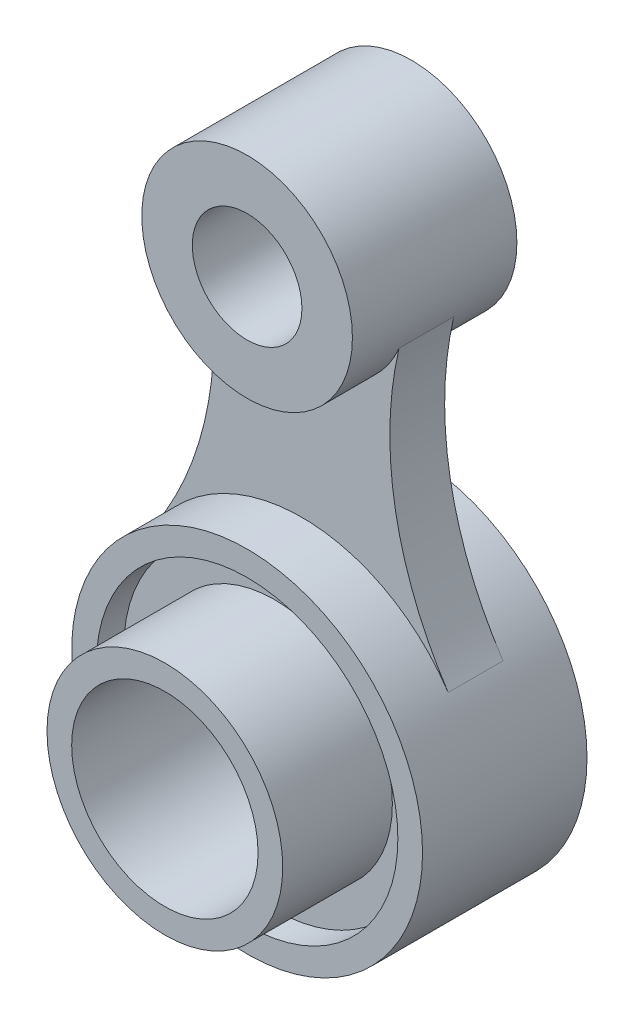
SolidWorks part; units mm, degrees
ref_plane "Front Plane" through (0, 0, 0) normal (0, 0, 1) x (1, 0, 0)
ref_plane "Top Plane" through (0, 0, 0) normal (0, 1, 0) x (1, 0, 0)
ref_plane "Right Plane" through (0, 0, 0) normal (1, 0, 0) x (0, 0, -1)
sketch "Sketch1" plane through (0, 0, 0) normal (0, 0, 1) x (1, 0, 0)
  line L0 (0, -38.5936) -> (0, 36.4064) construction
  circle A0 centre (0, -38.5936) radius 17
  circle A1 centre (0, -38.5936) radius 21.5
  circle A2 centre (0, -38.5936) radius 27.5
  arc A3 (-26.6783, -20.9225) -> (26.6783, -20.9225) centre (0, -38.5936) ccw
  arc A4 (18.3212, 31.3733) -> (-18.3212, 31.3733) centre (0, 36.4064) ccw
  circle A5 centre (0, 36.4064) radius 10
  arc A6 (26.6783, -20.9225) -> (18.3212, 31.3733) centre (80.0349, 14.4197) cw
  arc A7 (-26.6783, -20.9225) -> (-18.3212, 31.3733) centre (-80.0349, 14.4197) ccw
  circle A8 centre (0, 36.4064) radius 19.2117
  circle A9 centre (0, -38.5936) radius 32
  dimension "D1" = 34
  dimension "D2" = 43
  dimension "D3" = 55
  dimension "D4" = 64
  dimension "D5" = 38
  dimension "D6" = 20
  dimension "D8" = 64
  dimension "D7" = 75
extrude "Boss-Extrude1" add sketch "Sketch1" along normal blind 5 and the other way blind 5 contours A4 A7 A3 A6 | A2 | A5
extrude "Boss-Extrude3" add sketch "Sketch1<5>" along normal blind 15 and the other way blind 15 contours A9 | A8 | A2 | A5
sketch "Sketch1<5>" plane through (0, 0, 0) normal (0, 0, 1) x (1, 0, 0) same geometry as "Sketch1"
extrude "Boss-Extrude4" add sketch "Sketch1<6>" along normal blind 30 and the other way blind 15 separate body contours A0 | A1
sketch "Sketch1<6>" plane through (0, 0, 0) normal (0, 0, 1) x (1, 0, 0) same geometry as "Sketch1"
extrude "Boss-Extrude5" add sketch "Sketch1<7>" along normal blind 10 and the other way blind 15 contours A1 | A2
sketch "Sketch1<7>" plane through (0, 0, 0) normal (0, 0, 1) x (1, 0, 0) same geometry as "Sketch1"
